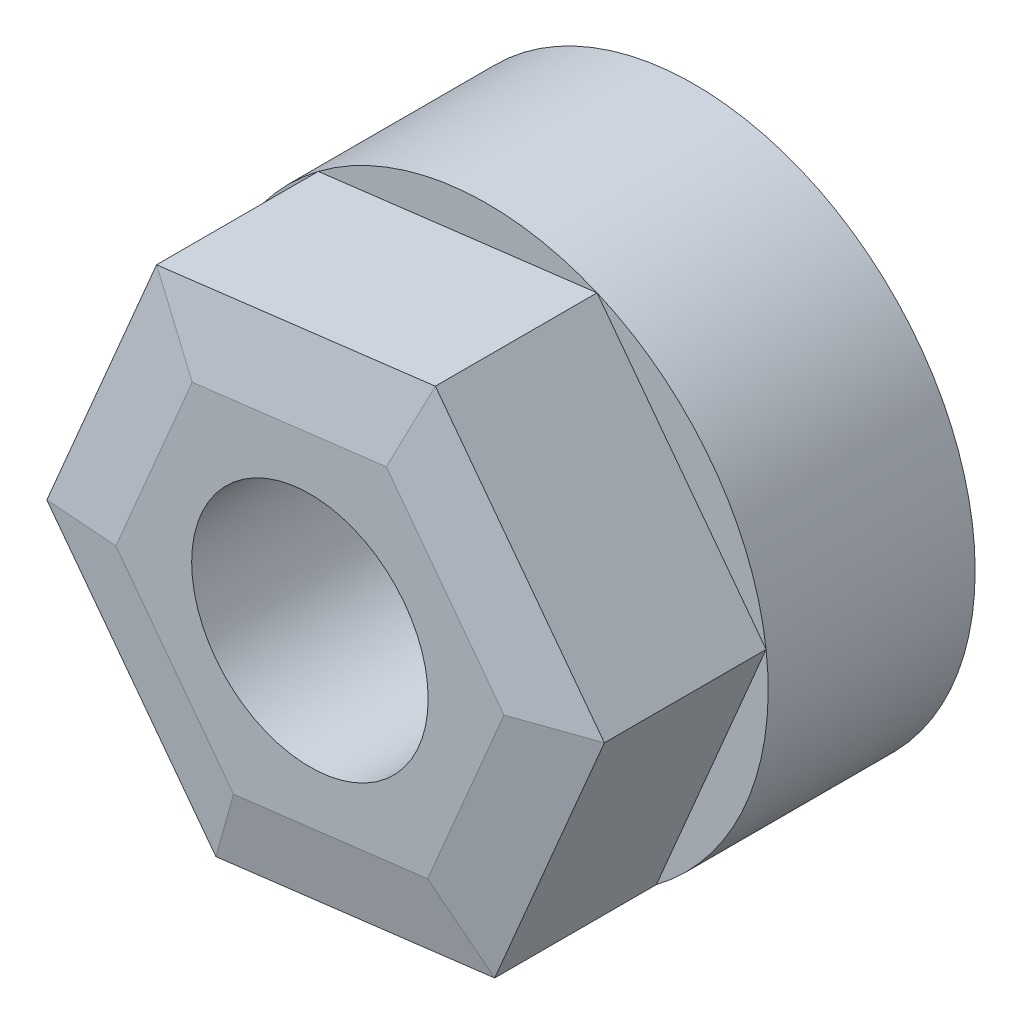
SolidWorks part; units mm, degrees
ref_plane "Alzado" through (0, 0, 0) normal (0, 0, 1) x (1, 0, 0)
ref_plane "Planta" through (0, 0, 0) normal (0, 1, 0) x (1, 0, 0)
ref_plane "Vista lateral" through (0, 0, 0) normal (1, 0, 0) x (0, 0, -1)
sketch "Croquis1" plane through (0, 0, 0) normal (0, 0, 1) x (1, 0, 0)
  circle A0 centre (0, 0) radius 9.5
  dimension "D1" = 19
extrude "Saliente-Extruir1" add sketch "Croquis1" along normal blind 7
sketch "Croquis2" plane through (0, 0, 7) normal (0, 0, 1) x (1, 0, 0)
  line L1 (3.7115, 8.745) -> (-5.7176, 7.5867)
  line L2 (-5.7176, 7.5867) -> (-9.4291, -1.1582)
  line L3 (-9.4291, -1.1582) -> (-3.7115, -8.745)
  line L4 (-3.7115, -8.745) -> (5.7176, -7.5867)
  line L5 (5.7176, -7.5867) -> (9.4291, 1.1582)
  line L6 (9.4291, 1.1582) -> (3.7115, 8.745)
  circle A0 centre (0, 0) radius 8.2272 construction
extrude "Saliente-Extruir2" add sketch "Croquis2" along normal blind 6
sketch "Croquis3" plane through (0, 0, 13) normal (0, 0, 1) x (1, 0, 0)
  circle A0 centre (0, 0) radius 4
  dimension "D1" = 8
extrude "Cortar-Extruir1" cut sketch "Croquis3" against normal through all
chamfer "Chaflán1" distance 2.5 angle 12 6 edges at (-7.5734, 3.2143, 13) (-1.0031, 8.1659, 13) (6.5703, 4.9516, 13) (7.5734, -3.2143, 13) (1.0031, -8.1659, 13) (-6.5703, -4.9516, 13) first distance on face at (4, 0, 13)
